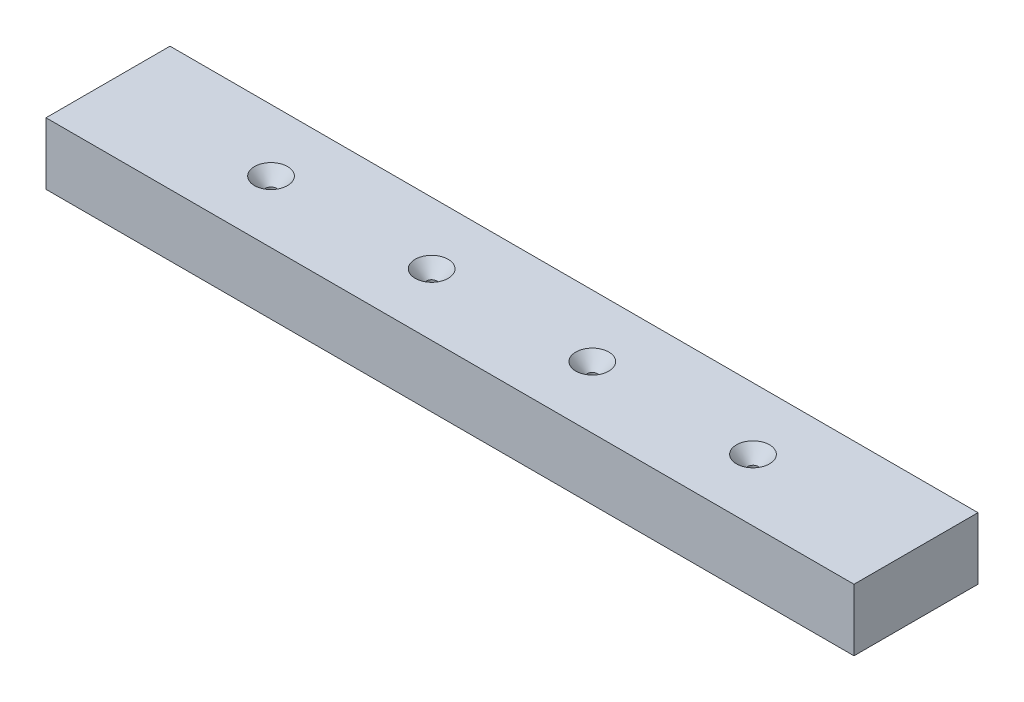
SolidWorks part; units mm, degrees
material "Beech"
ref_plane "Front Plane" through (0, 0, 0) normal (0, 0, 1) x (1, 0, 0)
ref_plane "Top Plane" through (0, 0, 0) normal (0, 1, 0) x (1, 0, 0)
ref_plane "Right Plane" through (0, 0, 0) normal (1, 0, 0) x (0, 0, -1)
sketch "Sketch1" plane through (0, 0, 0) normal (0, 0, 1) x (1, 0, 0)
  line L0 (248.25, 82.8417) -> (248.25, -188.5238) construction
  line L1 (248.25, 38.1) -> (0, 38.1)
  line L2 (248.25, 38.1) -> (248.25, 57.15)
  line L3 (248.25, 57.15) -> (0, 57.15)
  line L4 (0, 38.1) -> (0, 57.15)
  line L5 (-12.7, 38.1) -> (267.3, 38.1) construction
  line L6 (0, 82.8417) -> (0, -188.5238) construction
  dimension "D1" = 19.05
extrude "Boss-Extrude1" add sketch "Sketch1" along normal blind 38.1
hole_wizard "Hole1" positions "Sketch2" profile "Sketch3" legacy
sketch "Sketch2" plane through (-1090.5128, -52.975, -12.7) normal (0, 0, -1) x (0, 1, 0)
  line L0 (100.6, 1338.7628) -> (100.6, 1090.5128) construction
  line L6 (0.134, 1338.7628) -> (0.134, 1090.5128) construction
  point P12 (100.6, 1313.3628)
  point P14 (100.6, 1115.9128)
  point P16 (100.6, 1214.6378)
  point P22 (-100.332, 1214.6378)
  point P23 (-100.332, 1115.9128)
  point P24 (-100.332, 1313.3628)
sketch "Sketch3" plane through (222.85, -153.307, -12.7) normal (1, 0, 0) x (0, 1, 0)
  line L0 (0, 0) -> (0, 32.7039)
  line L1 (0, 32.7039) -> (1.5875, 31.75)
  line L2 (1.5875, 31.75) -> (1.5875, 4.0177)
  line L3 (1.5875, 4.0177) -> (5.08, 0)
  line L4 (5.08, 0) -> (0, 0)
  line L5 (0, -14.3089) -> (0, 102.4216) construction
  line L6 (0, 32.7039) -> (-1.5875, 31.75) construction
  line L7 (-1.5875, 4.0177) -> (-5.08, 0) construction
  dimension "Diameter" = 3.175
  dimension "Depth" = 31.75
  dimension "C-Sink Diameter" = 10.16
  dimension "C-Sink Angle" = 82
  dimension "Drill Angle" = 118
hole_wizard "Hole2" positions "Sketch4" profile "Sketch5" legacy
sketch "Sketch4" plane through (-1090.5128, 57.15, -415.7924) normal (0, 1, 0) x (0.3746, 0, 0.9272)
  line L0 (904.6882, 1078.3844) -> (811.6921, 848.211) construction
  line L4 (858.1902, 963.2977) -> (876.6817, 1009.0658)
  line L5 (876.6817, 1009.0658) -> (895.1732, 1054.8339)
  line L7 (858.1902, 963.2977) -> (875.853, 956.1614) construction
  point P20 (885.9274, 1031.9499)
  point P22 (867.4359, 986.1818)
  point P25 (830.4529, 894.6455)
  point P26 (848.9444, 940.4136)
sketch "Sketch5" plane through (99.4437, 57.15, 19.05) normal (1, 0, 0) x (0, 0, 1)
  line L0 (0, 0) -> (0, 58.1039)
  line L1 (0, 58.1039) -> (1.5875, 57.15)
  line L2 (1.5875, 57.15) -> (1.5875, 4.0177)
  line L3 (1.5875, 4.0177) -> (5.08, 0)
  line L4 (5.08, 0) -> (0, 0)
  line L5 (0, -14.3089) -> (0, 102.4216) construction
  line L6 (0, 58.1039) -> (-1.5875, 57.15) construction
  line L7 (-1.5875, 4.0177) -> (-5.08, 0) construction
  dimension "Diameter" = 3.175
  dimension "Depth" = 57.15
  dimension "C-Sink Diameter" = 10.16
  dimension "C-Sink Angle" = 82
  dimension "Drill Angle" = 118
